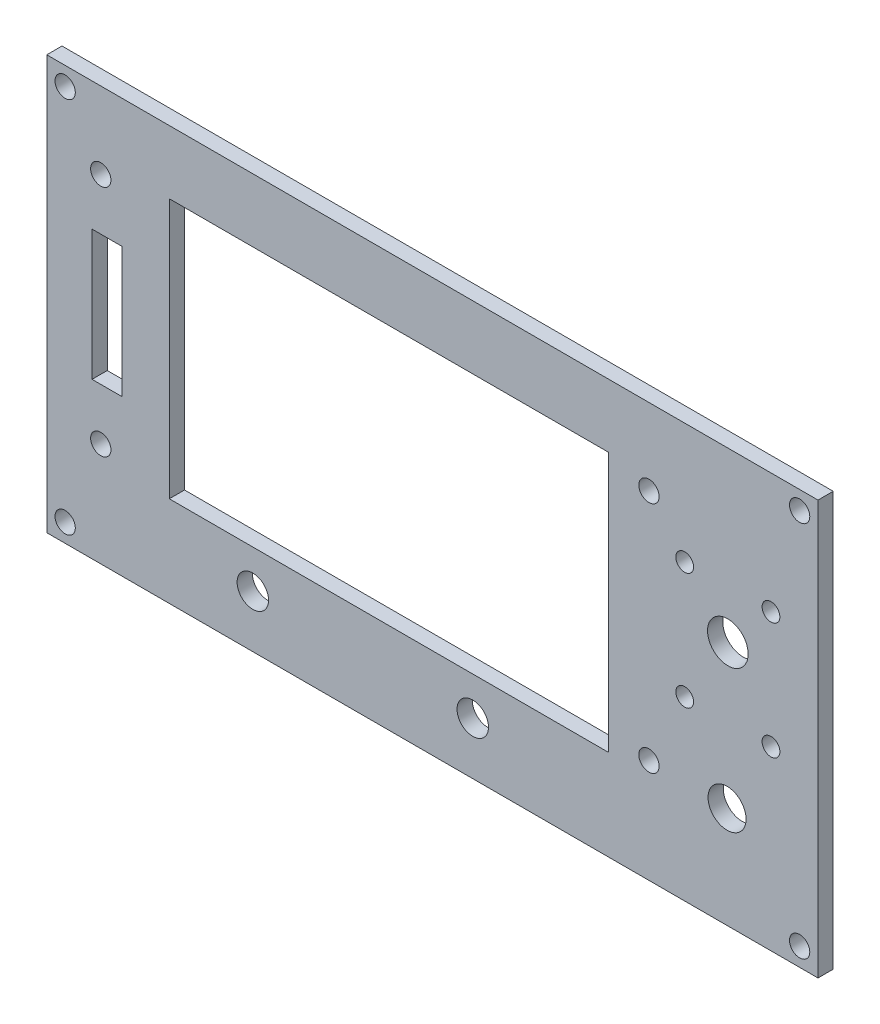
SolidWorks part; units mm, degrees
ref_plane "Plan de face" through (0, 0, 0) normal (0, 0, 1) x (1, 0, 0)
ref_plane "Plan de dessus" through (0, 0, 0) normal (0, 1, 0) x (1, 0, 0)
ref_plane "Plan de droite" through (0, 0, 0) normal (1, 0, 0) x (0, 0, -1)
sketch "Esquisse1" plane through (0, 0, -2.2) normal (0, 0, 1) x (1, 0, 0)
  line L0 (-15.1944, 26.9214) -> (-95.1944, 26.9214) construction
  line L1 (-119.8323, 39.9055) -> (32.1075, 39.9055)
  line L2 (-119.8323, 39.9055) -> (-119.8323, -41.6387)
  line L3 (-119.8323, -41.6387) -> (32.1075, -41.6387)
  line L4 (32.1075, 39.9055) -> (32.1075, -41.6387)
  line L5 (-95.6944, 27.4214) -> (-9.1944, 27.4214)
  line L6 (-95.6944, 27.4214) -> (-95.6944, -23.7786)
  line L7 (-95.6944, -23.7786) -> (-9.1944, -23.7786)
  line L8 (-9.1944, 27.4214) -> (-9.1944, -23.7786)
  line L9 (-95.1944, 26.9214) -> (-95.1944, -23.2786) construction
  line L10 (-15.1944, -23.2786) -> (-15.1944, 26.9214) construction
  line L11 (-95.1944, -23.2786) -> (-15.1944, -23.2786) construction
  line L12 (-112.5896, 39.9055) -> (-119.8323, 32.6629) construction
  line L13 (-110.9137, 14.6275) -> (-104.9761, 14.6275)
  line L14 (-110.9137, 14.6275) -> (-110.9137, -11.0054)
  line L15 (-110.9137, -11.0054) -> (-104.9761, -11.0054)
  line L16 (-104.9761, 14.6275) -> (-104.9761, -11.0054)
  line L17 (24.8649, 39.9055) -> (32.1075, 32.6629) construction
  line L18 (32.1075, -34.3961) -> (24.8649, -41.6387) construction
  line L19 (-112.5896, -41.6387) -> (-119.8323, -34.3961) construction
  circle A0 centre (-109.1944, 24.8214) radius 2
  circle A1 centre (-109.1944, -21.1786) radius 2
  circle A2 centre (-1.1944, -21.1786) radius 2
  circle A3 centre (-1.1944, 24.8214) radius 2
  circle A4 centre (-116.211, 36.2842) radius 2
  circle A5 centre (-116.211, -38.0174) radius 2
  circle A6 centre (28.4862, 36.2842) radius 2
  circle A7 centre (28.4862, -38.0174) radius 2
  circle A8 centre (14.3452, 6.7499) radius 4
  circle A9 centre (5.8452, 16.2043) radius 1.75
  circle A10 centre (22.8452, 16.2043) radius 1.75
  circle A11 centre (22.8452, -6.7957) radius 1.75
  circle A12 centre (5.8452, -6.7957) radius 1.75
  circle A13 centre (14.1946, -21.6387) radius 3.75
  circle A15 centre (-79.2375, -31.3167) radius 3.1
  circle A16 centre (-35.9056, -31.3167) radius 3.1
  circle A17 centre (-1.1944, 24.8214) radius 2 construction
  circle A18 centre (-79.2375, -31.3167) radius 3.1 construction
  circle A19 centre (-35.9056, -31.3167) radius 3.1 construction
  circle A20 centre (-1.1944, -21.1786) radius 2 construction
  circle A21 centre (-109.1944, -21.1786) radius 2 construction
  circle A22 centre (-109.1944, 24.8214) radius 2 construction
  dimension "D5" = 4
  dimension "D6" = 8
  dimension "D7" = 7.5
  dimension "D8" = 4
  dimension "D9" = 3.5
  dimension "D10" = 45
  dimension "D1" = 0.5
  dimension "D2" = 0.5
  dimension "D3" = 6
  dimension "D4" = 0.5
  dimension "D11" = 45
extrude "Boss.-Extru.1" add sketch "Esquisse1" along normal blind 3
